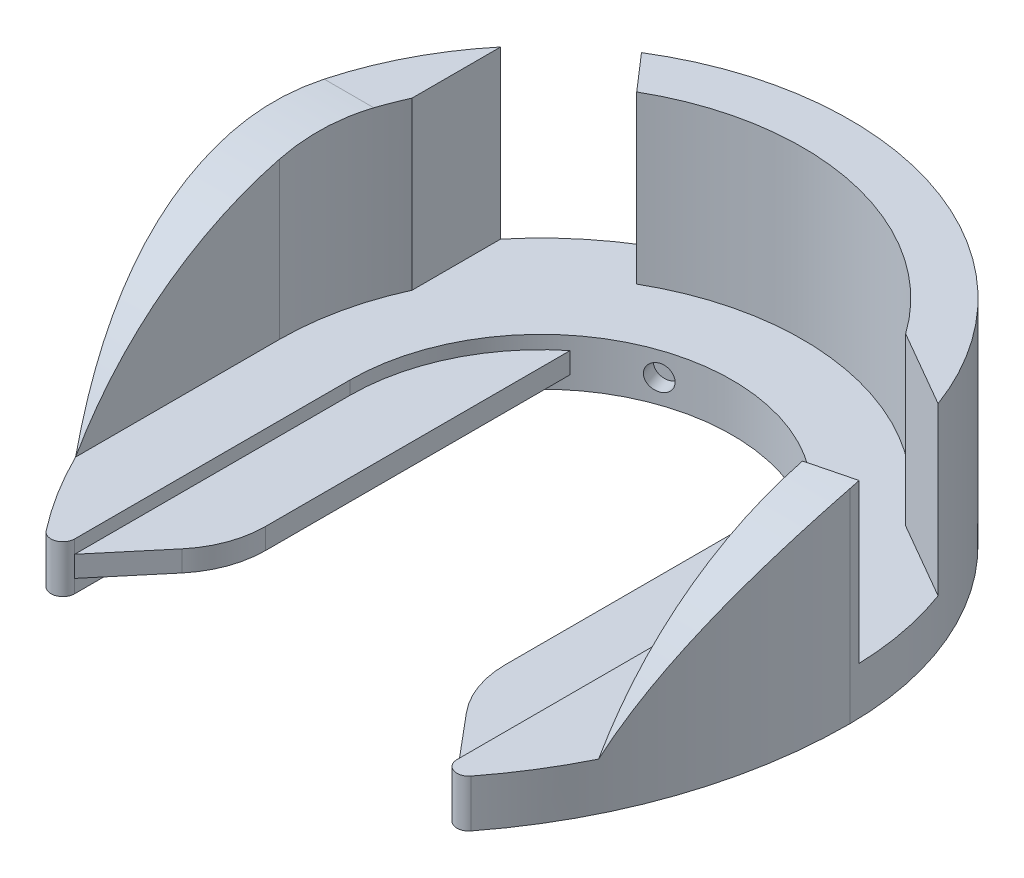
SolidWorks part; units mm, degrees
ref_plane "Front Plane" through (0, 0, 0) normal (0, 0, 1) x (1, 0, 0)
ref_plane "Top Plane" through (0, 0, 0) normal (0, 1, 0) x (1, 0, 0)
ref_plane "Right Plane" through (0, 0, 0) normal (1, 0, 0) x (0, 0, -1)
sketch "Sketch1" plane through (0, 0, 0) normal (0, 1, 0) x (1, 0, 0)
  line L3 (-40.2, 0) -> (-40.2, -57.8763)
  line L4 (40.2, 0) -> (40.2, -57.8763)
  line L5 (-25.2, -32.7206) -> (-25.2, 31.3209)
  line L6 (0, -55) -> (0, 55) construction
  line L7 (25.2, -32.7206) -> (25.2, 31.3209)
  line L8 (-40.2, -57.8763) -> (-29.8791, -45.5763)
  line L9 (40.2, -57.8763) -> (29.8791, -45.5763)
  line L10 (-55, 0) -> (-55, -42.8923)
  line L11 (55, 0) -> (55, -42.8923)
  arc A0 (65, 0) -> (-65, 0) centre (0, 0) ccw
  arc A1 (-65, 0) -> (65, 0) centre (0, 0) ccw construction
  arc A2 (40.2, 0) -> (-40.2, 0) centre (0, 0) ccw
  arc A3 (-65, 0) -> (-44.6761, -59.4076) centre (31.9875, 0) ccw
  arc A4 (65, 0) -> (44.6761, -59.4076) centre (-31.9875, 0) cw
  arc A5 (40.2, -57.8763) -> (44.6761, -59.4076) centre (42.7, -57.8763) ccw
  arc A6 (-40.2, -57.8763) -> (-44.6761, -59.4076) centre (-42.7, -57.8763) cw
  arc A8 (25.2, -32.7206) -> (29.8791, -45.5763) centre (45.2, -32.7206) ccw
  arc A9 (-25.2, -32.7206) -> (-29.8791, -45.5763) centre (-45.2, -32.7206) cw
  circle A10 centre (0, 0) radius 40.2 construction
  arc A11 (55, 0) -> (-55, 0) centre (0, 0) ccw
  point P9 (25.2, -40)
  point P19 (-25.2, -40)
  point P21 (0, 0)
  point P32 (55, -6.2824)
  point P33 (55, -24.7937)
  dimension "D1" = 130
  dimension "D2" = 80.4
  dimension "D4" = 2.5
  dimension "D6" = 40
  dimension "D7" = 20
  dimension "D8" = 80.4
  dimension "D9" = 110
  dimension "D3" = 50.4
  dimension "D5" = 40
extrude "Boss-Extrude1" add sketch "Sketch1" along normal blind 10 contours L11 A11 L10 A3 A6 L3 A2 L4 A5 A4 region at (-41.7941, 0, 28.9382)
extrude "Boss-Extrude2" add sketch "Sketch1<5>" along normal blind 4.4 from offset 2.8 contours A9 L5 A2 L3 L8 | L7 A8 L9 L4 A2 region at (-32.623, 0, 13.2342) region at (32.623, 0, 13.2342)
sketch "Sketch1<5>" plane through (0, 0, 0) normal (0, 1, 0) x (1, 0, 0) same geometry as "Sketch1"
extrude "Boss-Extrude3" add sketch "Sketch1<6>" along normal blind 45 contours A11 L11 A4 A0 A3 L10 region at (-60.8216, 0, 21.6377)
sketch "Sketch1<6>" plane through (0, 0, 0) normal (0, 1, 0) x (1, 0, 0) same geometry as "Sketch1"
sketch "Sketch2" plane through (0, 0, 0) normal (1, 0, 0) x (0, 0, -1)
  line L0 (-42.8923, 10) -> (-42.8923, 45)
  line L1 (-42.8923, 45) -> (17.1077, 45)
  arc A0 (-42.8923, 10) -> (17.1077, 45) centre (17.1077, -23.9286) cw
  point P4 (0, 0)
  point P5 (0, 0)
  dimension "D1" = 60
extrude "Cut-Extrude1" cut sketch "Sketch2" against normal through all both and the other way through all
sketch "Sketch3" plane through (0, 45, 0) normal (0, 1, 0) x (1, 0, 0)
  line L0 (-50.0125, 41.5181) -> (-43.3475, 33.8525) construction
  line L1 (-34.165, 55.297) -> (-27.5, 47.6314)
  line L2 (0, 0) -> (0, 65) construction
  line L3 (0, 0) -> (-42.6488, 49.0518) construction
  line L4 (-50.0125, 41.5181) -> (-50.0125, 22.8857)
  line L5 (64.9711, 1.9392) -> (55, 0)
  line L6 (60.962, 22.553) -> (44.8258, 31.8692)
  line L7 (60.962, 22.553) -> (50.9909, 20.6138) construction
  line L8 (0, 0) -> (63.8045, 12.4091) construction
  line L9 (0, 0) -> (-27.5, 47.6314) construction
  line L10 (0, 0) -> (55, 0) construction
  arc A0 (62.7083, 17.1077) -> (-62.7083, 17.1077) centre (0, 0) ccw construction
  arc A1 (52.2717, 17.1077) -> (-52.2717, 17.1077) centre (0, 0) ccw construction
  arc A2 (55, 0) -> (-55, 0) centre (0, 0) ccw construction
  arc A3 (-50.0125, 41.5181) -> (-34.165, 55.297) centre (0, 0) cw
  arc A4 (-27.5, 47.6314) -> (-43.3475, 33.8525) centre (0, 0) ccw
  arc A5 (-43.3475, 33.8525) -> (-50.0125, 22.8857) centre (0, 0) ccw
  arc A6 (60.962, 22.553) -> (64.9711, 1.9392) centre (0, 0) cw
  arc A7 (55, 0) -> (50.9909, 20.6138) centre (0, 0) ccw
  arc A8 (50.9909, 20.6138) -> (44.8258, 31.8692) centre (0, 0) ccw
  point P14 (55, 0)
  dimension "D4" = 2
  dimension "D1" = 21
  dimension "D3" = 10.5
  dimension "D5" = 120
extrude "Cut-Extrude2" cut sketch "Sketch3" against normal up to vertex (35 mm away) up to point (-55, 10, 0)
ref_axis "Axis1" through (0, -2.25, 0) along (0, 1, 0)
ref_plane "Plane1" through (0, 0, 0) normal (0.3256, 0, 0.9455) x (0, 1, 0)
sketch "Sketch7" plane through (0, 0, 0) normal (0.3256, 0, 0.9455) x (0, 1, 0)
  line L0 (10, -52.7592) -> (10, 10.4945) construction
  circle A0 centre (5, 0) radius 2.625
  point P2 (5.7602, 2.8153)
  dimension "D1" = 5.25
  dimension "D2" = 5
extrude "Cut-Extrude5" cut sketch "Sketch7" against normal blind 43.5
